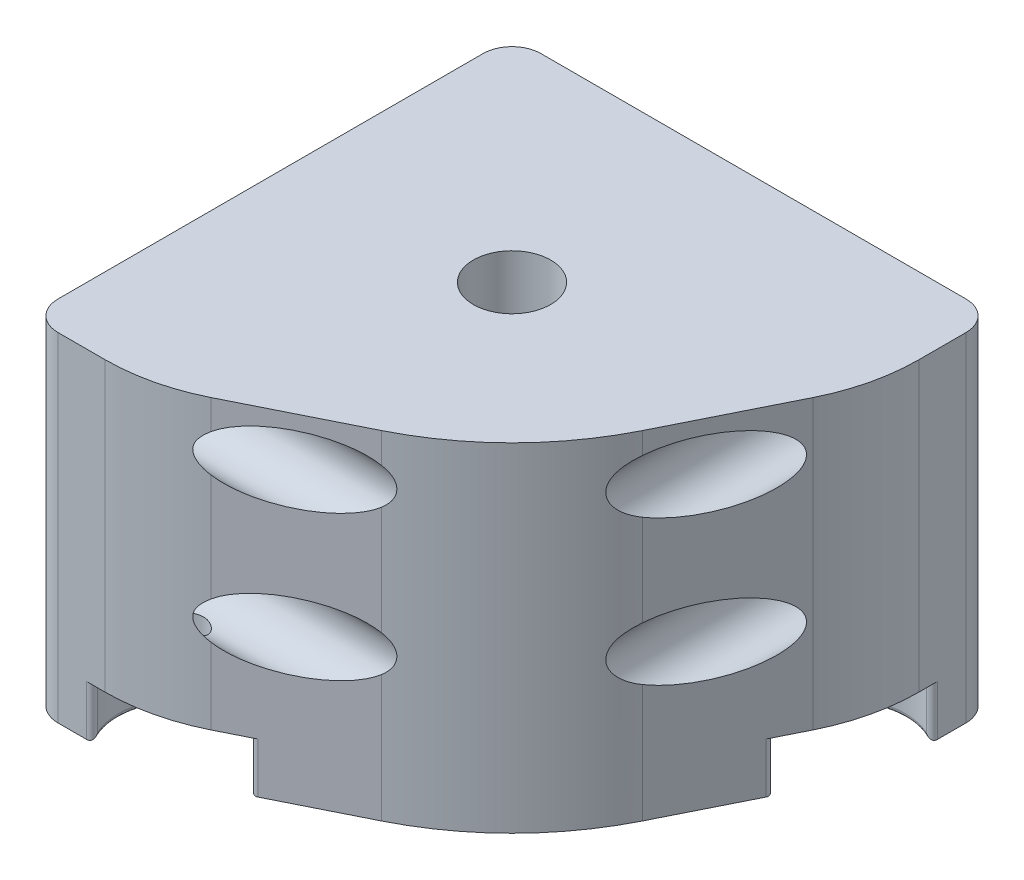
SolidWorks part; units mm, degrees
ref_plane "Plan de face" through (0, 0, 0) normal (0, 0, 1) x (1, 0, 0)
ref_plane "Plan de dessus" through (0, 0, 0) normal (0, 1, 0) x (1, 0, 0)
ref_plane "Plan de droite" through (0, 0, 0) normal (1, 0, 0) x (0, 0, -1)
sketch "Esquisse1" plane through (0, 0, 0) normal (0, 1, 0) x (1, 0, 0)
  line L0 (25, 25) -> (25, 30.1654) construction
  line L1 (-25, -25) -> (0.1127, -25)
  line L2 (-25, -25) -> (-25, 25)
  line L3 (-25, 25) -> (25, 25)
  line L4 (25, -0.1127) -> (25, 25)
  line L5 (-25, -25) -> (25, 25) construction
  line L6 (-25, 25) -> (25, -25) construction
  line L7 (25, 30.1654) -> (15, 30.1654) construction
  line L8 (15, 30.1654) -> (15, 25) construction
  line L9 (-25, -25) -> (-31.9159, -25) construction
  line L10 (-31.9159, -25) -> (-31.9159, -15) construction
  line L11 (-31.9159, -15) -> (-25, -15) construction
  line L12 (-25, -15) -> (25, -15) construction
  line L13 (15, 25) -> (15, -25) construction
  line L14 (0.1127, -25) -> (25, -0.1127) construction
  line L15 (25, -0.1127) -> (25, -25) construction
  line L16 (0.1127, -25) -> (25, -25) construction
  line L17 (-12.4437, -25) -> (-12.4437, -12.4437) construction
  line L18 (25, 12.4437) -> (12.4437, 12.4437) construction
  line L19 (12.5563, -12.5563) -> (-12.4437, -25)
  line L20 (12.5563, -12.5563) -> (25, 12.4437)
  circle A0 centre (-3, 3) radius 16 construction
  circle A1 centre (-3, 3) radius 4
  circle A2 centre (-12.4437, -20) radius 6.5 construction
  circle A3 centre (-12.4437, -20) radius 3 construction
  circle A4 centre (20, 12.4437) radius 3 construction
  circle A5 centre (20, 12.4437) radius 6.5 construction
  point P0 (0, 0)
  dimension "D2" = 32
  dimension "D4" = 8
  dimension "D5" = 22
  dimension "D6" = 13
  dimension "D7" = 6
  dimension "D1" = 50
  dimension "D3" = 22
  dimension "D8" = 5
  dimension "D9" = 12.5563
extrude "Boss.-Extru.1" add sketch "Esquisse1" along normal blind 35 contours L19 L20 L4 L3 L2 L1 A1 A3 A4 region at (-24.2929, 0, 0)
sketch "Esquisse16" plane through (0, 0, 0) normal (0, -1, 0) x (1, 0, 0)
  line L0 (-25, -25) -> (12.5563, 12.5563) construction
  line L1 (-25, 25) -> (25, -25) construction
  line L2 (-12.4437, 25) -> (-12.4437, 12.4437) construction
  line L3 (25, -12.4437) -> (12.4437, -12.4437) construction
  line L4 (-25, 25) -> (-12.4437, 25) construction
  circle A0 centre (-12.4437, 21.5) radius 2
  circle A1 centre (21.5, -12.4437) radius 2
  dimension "D1" = 4
  dimension "D2" = 4
  dimension "D3" = 3.5
  dimension "D4" = 3.5
  dimension "D5" = 90
extrude "Enlèv. mat.-Extru.8" cut sketch "Esquisse16" against normal blind 12
sketch "Esquisse2" plane through (0, 0, 0) normal (0, 1, 0) x (1, 0, 0)
  circle A0 centre (-3, 3) radius 16
  dimension "D1" = 32
extrude "Enlèv. mat.-Extru.1" cut sketch "Esquisse2" along normal blind 19
sketch "Esquisse4" plane through (-25, 0, 0) normal (-1, 0, 0) x (0, 0, 1)
  line L0 (20, 31.5) -> (20, 13.5) construction
  line L3 (25, 35) -> (25, 0) construction
  line L4 (25, 35) -> (-25, 35) construction
  line L5 (25, 0) -> (-25, 0) construction
  circle A0 centre (20, 30) radius 1.5
  circle A1 centre (20, 15) radius 1.5
  dimension "D2" = 3
  dimension "D1" = 5
  dimension "D3" = 5
  dimension "D4" = 15
extrude "Enlèv. mat.-Extru.2" cut sketch "Esquisse4" against normal up to surface (19.588 mm away) up to face at (0.0563, 17.5, 18.7782)
sketch "Esquisse5" plane through (0, 0, -25) normal (0, 0, -1) x (-1, 0, 0)
  line L0 (-19.1868, 31.5) -> (-19.1868, 13.5) construction
  line L1 (25, 35) -> (-25, 35) construction
  line L2 (25, 0) -> (-25, 0) construction
  circle A0 centre (-19.1868, 30) radius 1.5
  circle A1 centre (-19.1868, 15) radius 1.5
  dimension "D3" = 3
  dimension "D1" = 5
  dimension "D2" = 15
extrude "Enlèv. mat.-Extru.3" cut sketch "Esquisse5" against normal up to surface (27.2489 mm away) up to face at (18.7782, 17.5, 0.0563)
sketch "Esquisse15" plane through (0, 0, 0) normal (0, -1, 0) x (1, 0, 0)
  circle A2 centre (-12.4437, 21.5) radius 6.75
  circle A3 centre (21.5, -12.4437) radius 6.75
  dimension "D1" = 13.5
  dimension "D2" = 13.5
extrude "Enlèv. mat.-Extru.7" cut sketch "Esquisse15" against normal blind 5.2
sketch3d "Esquisse3D3" plane through (0, 0, 0) normal (0, 0, 1) x (1, 0, 0)
  dimension "D1" = 90
sketch "Esquisse11" plane through (-19, 0, 0) normal (1, 0, 0) x (0, 0, -1)
  circle A0 centre (-20, 30) radius 3.5
  circle A1 centre (-20, 15) radius 3.5
  dimension "D1" = 7
  dimension "D2" = 7
extrude "Enlèv. mat.-Extru.5" cut sketch "Esquisse11" along normal up to next
sketch "Esquisse13" plane through (0, 35, 0) normal (0, 1, 0) x (1, 0, 0)
  line L0 (25, 19) -> (-25, 19) construction
  line L1 (25, 12.4437) -> (25, 25) construction
  line L2 (-25, -25) -> (-25, 25) construction
  line L3 (-25, 25) -> (25, 25) construction
  dimension "D1" = 6
sketch3d "Esquisse3D5" plane through (0, 0, 0) normal (0, 0, 1) x (1, 0, 0)
  dimension "D1" = 90
sketch "Esquisse14" plane through (0, 0, -19) normal (0, 0, -1) x (-1, 0, 0)
  circle A0 centre (-19.1868, 30) radius 3.5
  circle A1 centre (-19.1868, 15) radius 3.5
  dimension "D1" = 7
  dimension "D2" = 7
extrude "Enlèv. mat.-Extru.6" cut sketch "Esquisse14" against normal up to next
fillet "Congé 1 2mm" radius 2 2 edges at (-3, 0, 13) (-3, 19, 13)
fillet "Congé 2 7mm" radius 7 1 edges at (-3, 19, 1)
fillet "Congé 4 30mm" radius 30 1 edges at (12.5563, 17.5, 12.5563)
fillet "Congé 5 20mm" radius 20 2 edges at (25, 20.1, -12.4437) (-12.4437, 20.1, 25)
fillet "Congé 6 3mm" radius 3 3 edges at (25, 17.5, -25) (-25, 17.5, -25) (-25, 17.5, 25)
fillet "Congé 8 0.5mm" radius 0.5 10 edges at (-25, 15, 21.5) (-25, 30, 21.5) (17.6868, 15, -25) (17.6868, 30, -25) (-14.1928, 0, 14.9806) (14.9806, 0, -14.1928) (21.6409, 2.6, -5.6951) (-5.6951, 2.6, 21.6409) (25, 2.6, -18.2153) (-18.2153, 2.6, 25)
